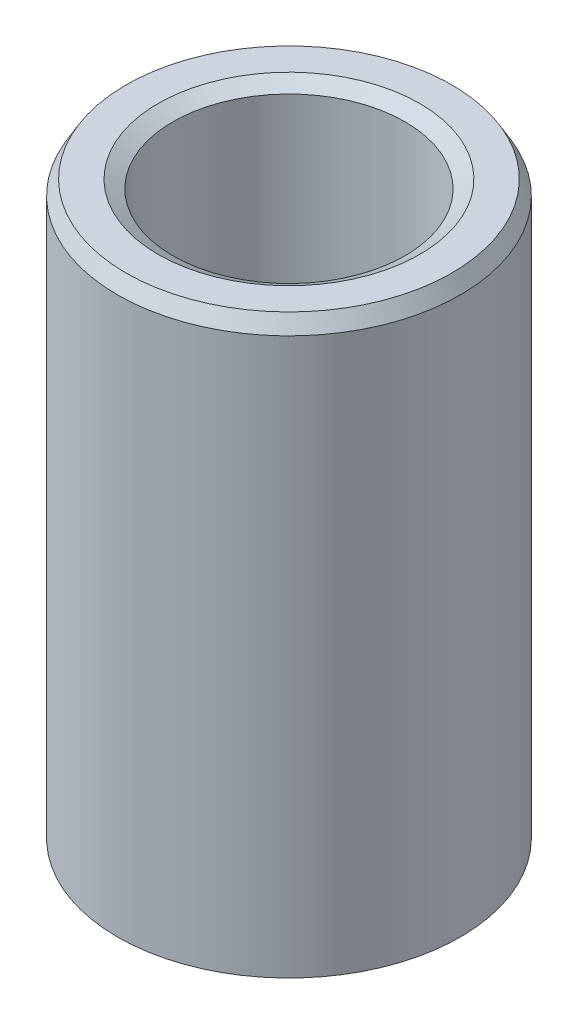
SolidWorks part; units mm, degrees
ref_plane "Front Plane" through (0, 0, 0) normal (0, 0, 1) x (1, 0, 0)
ref_plane "Top Plane" through (0, 0, 0) normal (0, 1, 0) x (1, 0, 0)
ref_plane "Right Plane" through (0, 0, 0) normal (1, 0, 0) x (0, 0, -1)
sketch "Sketch1" plane through (0, 0, 0) normal (0, 1, 0) x (1, 0, 0)
  circle A0 centre (0, 0) radius 17.5
  dimension "SLEEVE_OD" = 35
extrude "Boss-Extrude1" add sketch "Sketch1" along normal blind 59.1457
sketch "Sketch2" plane through (0, 0, 0) normal (0, 1, 0) x (1, 0, 0)
  circle A0 centre (0, 0) radius 11.8511
  dimension "BORE_D" = 23.7021
extrude "Cut-Extrude1" cut sketch "Sketch2" along normal through all
chamfer "Chamfer1" distance 1.5018 angle 30 4 edges at (0, 59.1457, 11.8511) (0, 0, 11.8511) (0, 0, 17.5) (0, 59.1457, 17.5) first distance on face at (0, 59.1457, 11.8511) first distance on face at (0, 0, 11.8511) first distance on face at (0, 59.1457, 17.5)
